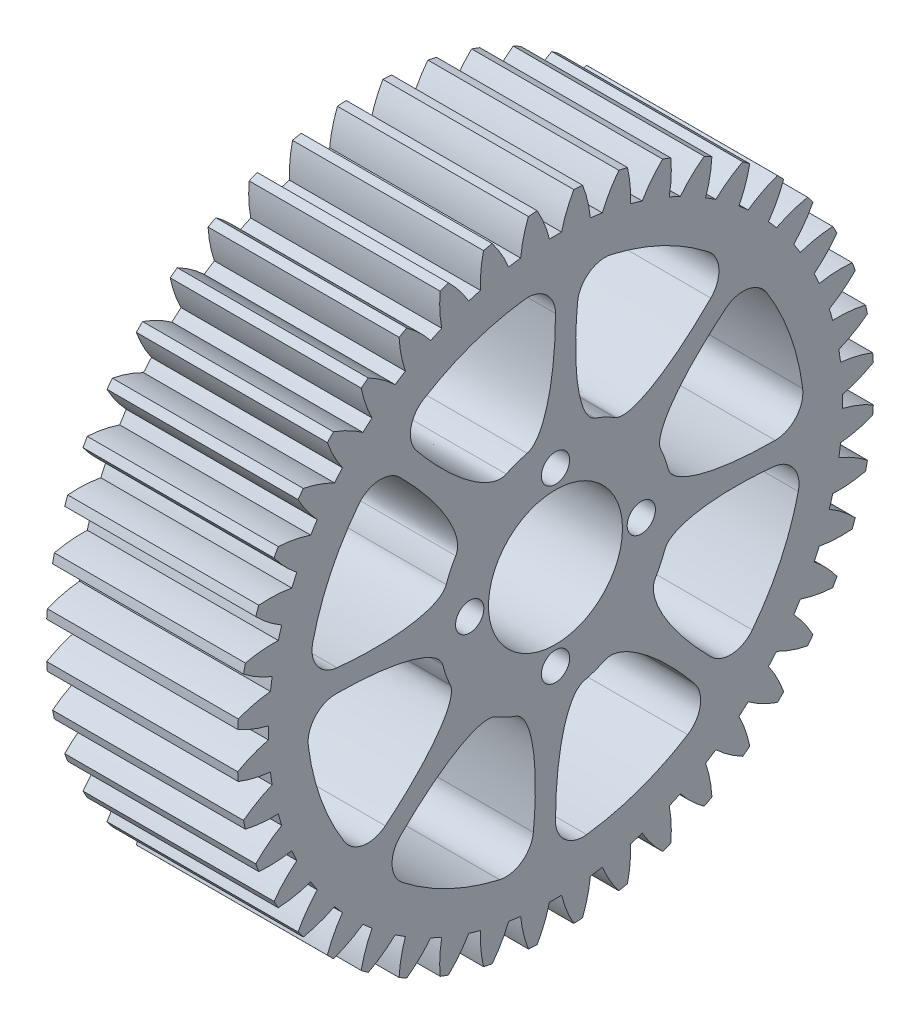
SolidWorks part; units mm, degrees
ref_plane "Plane1" through (0, 0, 0) normal (0, 0, 1) x (1, 0, 0)
ref_plane "Plane2" through (0, 0, 0) normal (0, 1, 0) x (1, 0, 0)
ref_plane "Plane3" through (0, 0, 0) normal (1, 0, 0) x (0, 0, -1)
other "Configuration Table"
sketch "HoldingSke" plane through (0, 0, 0) normal (0, 1, 0) x (1, 0, 0)
  line L0 (0, 0) -> (0.2877, -0.2779)
  line L1 (-15, 0) -> (100, 0) construction
  line L2 (0, 0) -> (-2.1039, 2.3779)
  line L3 (0, 0) -> (-11.863, 4.5341)
  line L4 (0, 0) -> (6.2122, 5.9991)
  line L5 (0, 0) -> (-46.8476, -17.4728)
  line L6 (0, 0) -> (-36.8888, -24.889)
  line L7 (-2.1039, 2.3779) -> (8.6586, 51.2059)
  line L8 (-76.2, 54.61) -> (-72.9, 54.61)
  line L9 (-71.009, 38.7566) -> (-53.1078, 45.2721)
  line L10 (-76.2, 71.12) -> (104.1128, 71.12)
  line L11 (0, 0) -> (-44.5, 0)
  line L12 (-76.2, 101.6) -> (-76.113, 101.6)
  line L13 (24.9733, 27.94) -> (52.9518, 28.4284)
  line L14 (24.9733, 27.94) -> (24.9743, 27.94)
  line L15 (24.9733, 27.94) -> (100.4006, 29.5858)
  line L16 (-63.627, -2.5) -> (-12.827, -2.5)
  circle A0 centre (0, 0) radius 12
  circle A1 centre (0, 0) radius 21
  circle A2 centre (0, 0) radius 21
  circle A3 centre (0, 0) radius 12
  dimension "Num_teeth" = 44
  dimension "Pitch_radius" = 180.3128
  dimension "Width" = 44.5
  dimension "Thickness" = 44.5
sketch "BasProSke" plane through (0, 0, 0) normal (0, 1, 0) x (1, 0, 0)
  line L0 (-10, 0) -> (60, 0) construction
  line L1 (0, 0) -> (0, 57.5)
  line L2 (0, 0) -> (44.5, 0)
  line L3 (44.5, 0) -> (44.5, 57.5)
  line L4 (44.5, 57.5) -> (0, 57.5)
  dimension "Thickness" = 44.5
  dimension "Diameter" = 115
revolve "Base-Revolve" add sketch "BasProSke" angle 360 about L0
sketch "TooCutSke" plane through (0, 0, 0) normal (1, 0, 0) x (0, 0, -1)
  line L1 (0, 0) -> (0, 107) construction
  line L2 (0, 0) -> (-2.1153, 54.9593) construction
  line L3 (0, 0) -> (-7.8431, 109.6602) construction
  line L4 (-2.1153, 54.9593) -> (-3.9215, 54.8301) construction
  arc A0 (1.0964, 51.8624) -> (-1.0964, 51.8624) centre (0, 0) ccw
  arc A1 (3.3223, 57.4294) -> (-3.3223, 57.4294) centre (0, 0) ccw
  circle A2 centre (0, 0) radius 55 construction
  circle A3 centre (0, 0) radius 51.6831 construction
  arc A4 (-1.0964, 51.8624) -> (-3.3223, 57.4294) centre (-22.4465, 46.5543) ccw
  arc A5 (3.3223, 57.4294) -> (1.0964, 51.8624) centre (22.4465, 46.5543) ccw
extrude "ToothCut" cut sketch "TooCutSke" along normal through all
fillet "Breaks" [suppressed] radius 0.05 tangent propagation no
fillet "RootFillets" [suppressed] radius 0.626
pattern_circular "TeethCuts" count 44 every 8.182 about axis through (-10, 0, 0) along (1, 0, 0) of "ToothCut", "RootFillets", "Breaks"
sketch "HubNeaOneSke" plane through (0, 0, 0) normal (-1, 0, 0) x (0, 0, 1)
  circle A0 centre (0, 0) radius 21
  dimension "Diameter" = 42
extrude "HubNearOne" add sketch "HubNeaOneSke" along normal blind 5.5001
sketch "HubNeaBotSke" plane through (0, 0, 0) normal (-1, 0, 0) x (0, 0, 1)
  circle A0 centre (0, 0) radius 21
  dimension "Diameter" = 42
extrude "HubNearBoth" [suppressed] add sketch "HubNeaBotSke" along normal blind 2.75
ref_plane "FarPln" through (44.5, 0, 0) normal (1, 0, 0) x (0, 0, -1)
sketch "HubFarSke" plane through (44.5, 0, 0) normal (1, 0, 0) x (0, 0, -1)
  circle A0 centre (0, 0) radius 21
  dimension "Diameter" = 42
extrude "HubFar" [suppressed] add sketch "HubFarSke" along normal blind 2.75
sketch "BorSke" plane through (0, 0, 0) normal (1, 0, 0) x (0, 0, -1)
  circle A0 centre (0, 0) radius 12
  dimension "Diameter" = 24
extrude "Bore" cut sketch "BorSke" along normal mid plane 100.0001
sketch "KeySke" plane through (0, 0, 0) normal (1, 0, 0) x (0, 0, -1)
  line L0 (-4, 0) -> (-4, 15.3)
  line L1 (-4, 15.3) -> (4, 15.3)
  line L2 (4, 15.3) -> (4, 0)
  line L3 (0, 0) -> (0, 34) construction
  line L4 (-4, 0) -> (4, 0)
  dimension "Width" = 8
extrude "Keyway" [suppressed] cut sketch "KeySke" along normal mid plane 100.0001
pattern_circular "Keyway2" [suppressed] count 2 every 90 about axis through (-10, 0, 0) along (1, 0, 0) reverse direction yes
sketch "Sketch5" plane through (0, 0, 0) normal (-1, 0, 0) x (0, 0, 1)
  line L0 (0, 21) -> (0, 45)
  line L1 (14.8492, 14.8492) -> (31.8198, 31.8198)
  line L2 (21, 0) -> (45, 0)
  line L3 (14.8492, -14.8492) -> (31.8198, -31.8198)
  line L4 (0, -21) -> (0, -45)
  line L5 (-14.8492, -14.8492) -> (-31.8198, -31.8198)
  line L6 (-21, 0) -> (-45, 0)
  line L7 (-14.8492, 14.8492) -> (-31.8198, 31.8198)
  line L8 (-4.5356, 44.7708) -> (-2.1166, 20.8931)
  line L9 (28.4506, 34.8649) -> (13.2769, 16.2703)
  line L10 (44.7708, 4.5356) -> (20.8931, 2.1166)
  line L11 (34.8649, -28.4506) -> (16.2703, -13.2769)
  line L12 (4.5356, -44.7708) -> (2.1166, -20.8931)
  line L13 (-28.4506, -34.8649) -> (-13.2769, -16.2703)
  line L14 (-44.7708, -4.5356) -> (-20.8931, -2.1166)
  line L15 (-34.8649, 28.4506) -> (-16.2703, 13.2769)
  arc A0 (-34.8649, 28.4506) -> (-45, 0) centre (0, 0) ccw
  arc A1 (-16.2703, 13.2769) -> (-21, 0) centre (0, 0) ccw
  arc A2 (-4.5356, 44.7708) -> (-31.8198, 31.8198) centre (0, 0) ccw
  arc A3 (-2.1166, 20.8931) -> (-14.8492, 14.8492) centre (0, 0) ccw
  arc A4 (13.2769, 16.2703) -> (0, 21) centre (0, 0) ccw
  arc A5 (28.4506, 34.8649) -> (0, 45) centre (0, 0) ccw
  arc A6 (20.8931, 2.1166) -> (14.8492, 14.8492) centre (0, 0) ccw
  arc A7 (44.7708, 4.5356) -> (31.8198, 31.8198) centre (0, 0) ccw
  arc A8 (16.2703, -13.2769) -> (21, 0) centre (0, 0) ccw
  arc A9 (34.8649, -28.4506) -> (45, 0) centre (0, 0) ccw
  arc A10 (2.1166, -20.8931) -> (14.8492, -14.8492) centre (0, 0) ccw
  arc A11 (4.5356, -44.7708) -> (31.8198, -31.8198) centre (0, 0) ccw
  arc A12 (-13.2769, -16.2703) -> (0, -21) centre (0, 0) ccw
  arc A13 (-28.4506, -34.8649) -> (0, -45) centre (0, 0) ccw
  arc A14 (-20.8931, -2.1166) -> (-14.8492, -14.8492) centre (0, 0) ccw
  arc A15 (-44.7708, -4.5356) -> (-31.8198, -31.8198) centre (0, 0) ccw
  point P22 (0, 0)
  point P40 (0, 0)
  dimension "D1" = 8
  dimension "D2" = 8
extrude "Cut-Extrude1" cut sketch "Sketch5" against normal through all
fillet "Fillet2" radius 10 8 edges at (22.25, 2.1166, 20.8931) (22.25, -13.2769, 16.2703) (22.25, -20.8931, 2.1166) (22.25, -16.2703, -13.2769) (22.25, -2.1166, -20.8931) (22.25, 13.2769, -16.2703) (22.25, 20.8931, -2.1166) (22.25, 16.2703, 13.2769) second distance 20 first distance on face at (-5.5001, 0, 21)
fillet "Fillet3" radius 20 8 edges at (22.25, 14.8492, -14.8492) (22.25, 21, 0) (22.25, 14.8492, 14.8492) (22.25, 0, 21) (22.25, -14.8492, 14.8492) (22.25, -21, 0) (22.25, -14.8492, -14.8492) (22.25, 0, -21) second distance 10 first distance on face at (22.25, 23.3345, -23.3345) first distance on face at (22.25, 33, 0) first distance on face at (22.25, 23.3345, 23.3345) first distance on face at (22.25, 0, 33) first distance on face at (22.25, -23.3345, 23.3345) first distance on face at (22.25, -33, 0) first distance on face at (22.25, -23.3345, -23.3345) first distance on face at (22.25, 0, -33)
fillet "Fillet4" radius 5 16 edges at (22.25, 31.8198, 31.8198) (22.25, 0, 45) (22.25, -28.4506, 34.8649) (22.25, -31.8198, 31.8198) (22.25, -44.7708, 4.5356) (22.25, -45, 0) (22.25, -34.8649, -28.4506) (22.25, -31.8198, -31.8198) (22.25, -4.5356, -44.7708) (22.25, 0, -45) (22.25, 28.4506, -34.8649) (22.25, 31.8198, -31.8198) (22.25, 45, 0) (22.25, 44.7708, -4.5356) (22.25, 34.8649, 28.4506) (22.25, 4.5356, 44.7708)
sketch "Sketch6" plane through (44.5, 0, 0) normal (1, 0, 0) x (0, 0, -1)
  circle A0 centre (0, 0) radius 57.5
extrude "Cut-Extrude2" cut sketch "Sketch6" against normal blind 10
sketch "Sketch7" plane through (34.5, 0, 0) normal (1, 0, 0) x (0, 0, -1)
  circle A0 centre (0, 0) radius 12.1
extrude "Cut-Extrude3" cut sketch "Sketch7" against normal through all
sketch "Sketch8" plane through (34.5, 0, 0) normal (1, 0, 0) x (0, 0, -1)
  circle A1 centre (0, 15.5) radius 2.55
extrude "Cut-Extrude4" cut sketch "Sketch8" against normal through all
pattern_circular "CirPattern1" count 4 over 360 about axis through (34.5, 0, 0) along (1, 0, 0) of "Cut-Extrude4"
equation "' \"Module@HoldingSke\" = 6.35"
equation "' \"Num_teeth@HoldingSke\" = 12"
equation "' \"Ap@HoldingSke\" =  20"
equation "' \"Ap@HoldingSke\" = 20"
equation "' \"Width@HoldingSke\" = 0.5 * 25.4"
equation "' \"Hub_dia@HoldingSke\"= 1 * 25.4"
equation "' \"Hub_dia@HoldingSke\" = 1 * 25.4"
equation "' \"Overall_len@HoldingSke\" = 1.0 * 25.4"
equation "' \"Bore@HoldingSke\" = 0.75 * 25.4"
equation "' \"T_dim@HoldingSke\" = 0.1 * 25.4"
equation "' \"Width@KeySke\" = 0.25 * 25.4"
equation "' \"Show_teeth@HoldingSke\" = 13"
equation "' \"Backlash@HoldingSke\" = 0.009 * 25.4"
equation "' \"Addendum_fac@HoldingSke\" = 1.0"
equation "' \"Dedendum_fac@HoldingSke\" = 1.25"
equation "' \"Dedendum_add@HoldingSke\" = 0.00005 * 25.4"
equation "' \"Clearance_fac@HoldingSke\" = 0.25"
equation "\"Pitch@HoldingSke\" = 1 / \"Module@HoldingSke\""
equation "\"Overcut_dia@TooCutSke\" = (\"Num_teeth@HoldingSke\" + 2 * \"Addendum_fac@HoldingSke\") / \"Pitch@HoldingSke\" + 0.002 * 25.4"
equation "\"Pitch_dia@TooCutSke\" = \"Num_teeth@HoldingSke\" / \"Pitch@HoldingSke\""
equation "\"Base_dia@TooCutSke\" = \"Num_teeth@HoldingSke\" / \"Pitch@HoldingSke\" * cos((\"Ap@HoldingSke\"  * 3.14159265 / 180))"
equation "\"Root_dia@TooCutSke\" = (\"Num_teeth@HoldingSke\" + 2) / \"Pitch@HoldingSke\" - 2 * (\"Addendum_fac@HoldingSke\" + \"Dedendum_fac@HoldingSke\") / \"Pitch@HoldingSke\" - \"Dedendum_add@HoldingSke\" * 2"
equation "\"Half_ang@TooCutSke\" = 180 / \"Num_teeth@HoldingSke\""
equation "\"Half_CT@TooCutSke\" = \"Num_teeth@HoldingSke\" / \"Pitch@HoldingSke\" * sin((3.14159265 / 2 / \"Num_teeth@HoldingSke\")) / 2 - 7 * \"Backlash@HoldingSke\" / 4"
equation "\"Flank_rad@TooCutSke\" = \"Num_teeth@HoldingSke\" / \"Pitch@HoldingSke\" / 5"
equation "\"Radius@RootFillets\" = \"Clearance_fac@HoldingSke\" / \"Pitch@HoldingSke\" + \"Dedendum_add@HoldingSke\""
equation "\"Break_rad@Breaks\" = 0.02 / \"Pitch@HoldingSke\""
equation "\"Thickness@HoldingSke\" = \"Width@HoldingSke\""
equation "\"OAL@HoldingSke\" = \"Thickness@HoldingSke\""
equation "\"MHD@HoldingSke\" = (\"Num_teeth@HoldingSke\" + 2) / \"Pitch@HoldingSke\" - 2 * (\"Addendum_fac@HoldingSke\" + \"Dedendum_fac@HoldingSke\")  / \"Pitch@HoldingSke\" - \"Dedendum_add@HoldingSke\" * 2"
equation "\"MBD@HoldingSke\" = (\"Num_teeth@HoldingSke\" + 2) / \"Pitch@HoldingSke\" - 2 * (\"Addendum_fac@HoldingSke\" + \"Dedendum_fac@HoldingSke\")  / \"Pitch@HoldingSke\" - \"Dedendum_add@HoldingSke\" * 2 - 0.002 * 25.4"
equation "\"MHD@HoldingSke\" = ((sgn( \"MHD@HoldingSke\" - \"Hub_dia@HoldingSke\" )-1)*( \"MHD@HoldingSke\" - \"Hub_dia@HoldingSke\" ))/-2+ \"Hub_dia@HoldingSke\""
equation "\"MBD@HoldingSke\" = ((sgn( \"MBD@HoldingSke\" - \"Bore@HoldingSke\" )-1)*( \"MBD@HoldingSke\" - \"Bore@HoldingSke\" ))/-2+ \"Bore@HoldingSke\""
equation "\"OAL@HoldingSke\" = ((sgn( \"OAL@HoldingSke\" - \"Overall_len@HoldingSke\" )+1)*( \"OAL@HoldingSke\" - \"Overall_len@HoldingSke\" ))/2 + \"Overall_len@HoldingSke\" + 0.000002 * 25.4"
equation "\"Num_teeth@TeethCuts\" = int( \"Show_teeth@HoldingSke\" ) + 1"
equation "\"Num_teeth@TeethCuts\" = ((sgn( \"Num_teeth@TeethCuts\" - \"Num_teeth@HoldingSke\" )-1)*( \"Num_teeth@TeethCuts\" - \"Num_teeth@HoldingSke\" ))/-2+ \"Num_teeth@HoldingSke\""
equation "\"Num_teeth@TeethCuts\" = ((sgn( \"Num_teeth@TeethCuts\" - 2.0)+1)*( \"Num_teeth@TeethCuts\" - 2.0))/2 +2.0"
equation "\"Angle@TeethCuts\" = 360.0 / \"Num_teeth@HoldingSke\""
equation "\"Diameter@BasProSke\" = (\"Num_teeth@HoldingSke\" + 2 * \"Addendum_fac@HoldingSke\") / \"Pitch@HoldingSke\""
equation "\"Thickness@BasProSke\"  = \"Thickness@HoldingSke\""
equation "' \"Fillet_rad@BasProSke\" =  \"Thickness@HoldingSke\" * 0.05"
equation "' \"Fillet_rad@BasProSke\" = \"Thickness@HoldingSke\" * 0.05"
equation "\"MHD@HoldingSke\" = ((sgn( \"MHD@HoldingSke\" - \"Root_dia@TooCutSke\" )-1)*( \"MHD@HoldingSke\" - \"Root_dia@TooCutSke\" ))/-2+ \"Root_dia@TooCutSke\""
equation "\"Diameter@HubNeaOneSke\" = \"MHD@HoldingSke\""
equation "\"Length@HubNearOne\" = \"OAL@HoldingSke\" - \"Thickness@BasProSke\""
equation "\"Diameter@HubNeaBotSke\" = \"MHD@HoldingSke\""
equation "\"Length@HubNearBoth\" = ( \"OAL@HoldingSke\" - \"Thickness@BasProSke\" ) / 2.0"
equation "\"Thickness@FarPln\" = \"Thickness@BasProSke\""
equation "\"Diameter@HubFarSke\" = \"MHD@HoldingSke\""
equation "\"Length@HubFar\" = ( \"OAL@HoldingSke\" - \"Thickness@BasProSke\" ) / 2.0"
equation "\"Diameter@BorSke\" = \"MBD@HoldingSke\""
equation "\"D1@Bore\" = \"OAL@HoldingSke\" * 2.0"
equation "\"D1@Keyway\" = \"OAL@HoldingSke\" * 2.0"
equation "\"Offset@KeySke\" = \"T_dim@HoldingSke\" + \"MBD@HoldingSke\" / 2.0"
